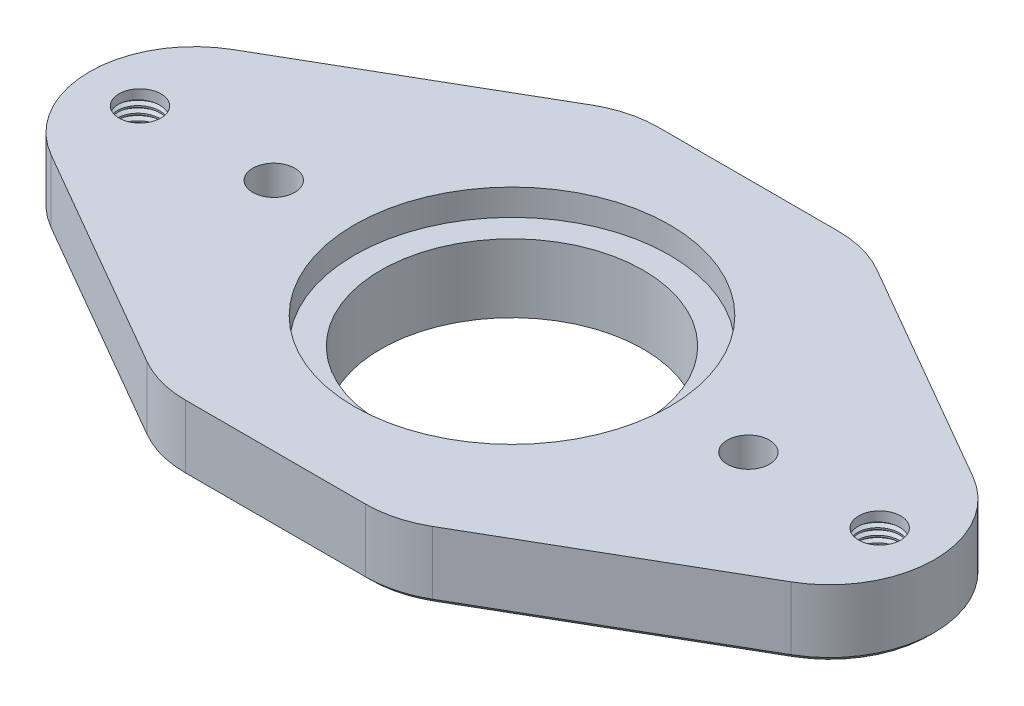
SolidWorks part; units mm, degrees
ref_plane "Plano frontal" through (0, 0, 0) normal (0, 0, 1) x (1, 0, 0)
ref_plane "Plano superior" through (0, 0, 0) normal (0, 1, 0) x (1, 0, 0)
ref_plane "Plano direito" through (0, 0, 0) normal (1, 0, 0) x (0, 0, -1)
sketch "Esboço1" plane through (0, 0, 0) normal (0, 1, 0) x (1, 0, 0)
  line L0 (22.5, 45) -> (100.4423, 0)
  line L1 (-22.5, 45) -> (22.5, 45)
  line L3 (-22.5, -45) -> (22.5, -45)
  line L5 (-22.5, 45) -> (22.5, -45) construction
  line L6 (-22.5, -45) -> (22.5, 45) construction
  line L7 (100.4423, 0) -> (22.5, -45)
  line L8 (-22.5, 45) -> (-100.4423, 0)
  line L9 (-22.5, -45) -> (-100.4423, 0)
  line L10 (0, 51.2716) -> (0, -62.3374) construction
  line L11 (-115.2689, 0) -> (116.7443, 0) construction
  point P0 (0, 0)
  dimension "D1" = 45
  dimension "D2" = 90
  dimension "D3" = 90
  dimension "D4" = 90
  dimension "D5" = 90
  dimension "D6" = 90
  dimension "D7" = 200.8846
extrude "Ressalto-extrusão1" add sketch "Esboço1" along normal blind 18
fillet "Filete1" radius 20 1 edges at (-100.4423, 9, 0)
fillet "Filete2" radius 20 1 edges at (-22.5, 9, 45)
fillet "Filete3" radius 20 1 edges at (22.5, 9, 45)
fillet "Filete4" radius 20 1 edges at (100.4423, 9, 0)
fillet "Filete5" radius 20 1 edges at (22.5, 9, -45)
fillet "Filete6" radius 20 1 edges at (-22.5, 9, -45)
sketch "Esboço2" plane through (0, 0, 0) normal (0, 1, 0) x (1, 0, 0)
  line L0 (-95.225, 0) -> (82.7172, 0) construction
  line L1 (-17.5, 35) -> (17.5, 35)
  line L3 (-17.5, -35) -> (17.5, -35)
  line L5 (-17.5, 35) -> (17.5, -35) construction
  line L6 (-17.5, -35) -> (17.5, 35) construction
  line L7 (17.5, -35) -> (78.1218, 0)
  line L8 (78.1218, 0) -> (17.5, 35)
  line L9 (-17.5, -35) -> (-78.1218, 0)
  line L10 (-78.1218, 0) -> (-17.5, 35)
  point P0 (0, 0)
  dimension "D1" = 70
  dimension "D2" = 35
  dimension "D3" = 70
  dimension "D4" = 70
  dimension "D5" = 70
  dimension "D6" = 70
extrude "Corte-extrusão1" cut sketch "Esboço2" along normal blind 5 flip side to cut
fillet "Filete7" radius 20 1 edges at (-17.5, 2.5, -35)
fillet "Filete8" radius 20 1 edges at (17.5, 2.5, -35)
fillet "Filete9" radius 20 1 edges at (78.1218, 2.5, 0)
fillet "Filete10" radius 20 1 edges at (-78.1218, 2.5, 0)
fillet "Filete11" radius 20 1 edges at (-17.5, 2.5, 35)
fillet "Filete12" radius 20 1 edges at (17.5, 2.5, 35)
sketch "Esboço3" plane through (0, 0, 0) normal (0, -1, 0) x (1, 0, 0)
  line L0 (0, 51.4475) -> (0, -49.7955) construction
  line L1 (-88.6171, 0.826) -> (83.6612, 0.826) construction
  line L2 (-70, 8.4959) -> (-70, -5.6639) construction
  line L3 (-45, 6.3719) -> (-45, -5.6639) construction
  circle A0 centre (-45, 0.354) radius 4
  circle A1 centre (-70, 0.826) radius 4
  dimension "D3" = 8
  dimension "D4" = 8
  dimension "D1" = 45
  dimension "D2" = 70
extrude "Corte-extrusão2" cut sketch "Esboço3" against normal blind 19 contours A1 | A0
sketch "Esboço4" plane through (0, 0, 0) normal (0, 1, 0) x (1, 0, 0)
  line L0 (-83.8971, 0) -> (85.3131, 0) construction
  line L1 (0, -48.6062) -> (0, 52.999) construction
  line L2 (45, -4.827) -> (45, 7.8151) construction
  line L3 (70, -4.827) -> (70, 7.8151) construction
  circle A0 centre (45, 0) radius 4
  circle A1 centre (70, 0) radius 4
  dimension "D3" = 8
  dimension "D4" = 8
  dimension "D1" = 45
  dimension "D2" = 70
extrude "Corte-extrusão4" cut sketch "Esboço4" along normal blind 19
sketch "Esboço5" plane through (0, 18, 0) normal (0, 1, 0) x (1, 0, 0)
  circle A0 centre (0, 0) radius 25
  dimension "D1" = 50
extrude "Corte-extrusão5" cut sketch "Esboço5" against normal blind 19
sketch "Esboço6" plane through (0, 18, 0) normal (0, 1, 0) x (1, 0, 0)
  circle A0 centre (0, 0) radius 30
  dimension "D1" = 60
extrude "Corte-extrusão6" cut sketch "Esboço6" against normal blind 5
sketch "Esboço8" plane through (0, 0, 0) normal (0, 0, 1) x (1, 0, 0)
  line L0 (-25, 0) -> (25, 0) construction
  line L1 (30, -0.5) -> (28, -0.5)
  line L2 (30, -0.5) -> (30, 1.5)
  line L3 (30, 1.5) -> (28, 1.5)
  line L4 (28, -0.5) -> (28, 1.5)
  line L5 (0, -5.8797) -> (0, 20.9238) construction
  dimension "D1" = 28
  dimension "D2" = 2
  dimension "D3" = 1.5
revolve "Corte-Revolução1" cut sketch "Esboço8" angle 360 about L5
chamfer "Chanfro1" distance 1 angle 45 28 edges at (45, 0, 4) (-45, 0, -3.646) (-70, 5, 4.826) (70, 5, 4) (0, 5, -45) (22.3174, 5, -44.3185) (-22.3174, 5, -44.3185) (48.7917, 5, -29.8205) (-48.7917, 5, -29.8205) (80.4423, 5, 0) (48.7917, 5, 29.8205) (22.3174, 5, 44.3185) (0, 5, 45) (-22.3174, 5, 44.3185) (-48.7917, 5, 29.8205) (-80.4423, 5, 0) (0, 0, -35) (-17.3174, 0, -34.3185) (17.3174, 0, -34.3185) (-35.1314, 0, -24.8205) (35.1314, 0, -24.8205) (-58.1218, 0, 0) (-35.1314, 0, 24.8205) (-17.3174, 0, 34.3185) (0, 0, 35) (17.3174, 0, 34.3185) (35.1314, 0, 24.8205) (58.1218, 0, 0)
thread "Rosca1" pitch 1.25 method cut profile "Perfil da rosca3" start angle 0, offset 0, length 10, pitch 1.25, diameter 8
ref_plane "Plano3" through (74, 6, 0) normal (0, 0, 1) x (1, 0, 0)
sketch "Perfil da rosca3" plane through (74, 6, 0) normal (0, 0, 1) x (1, 0, 0)
  line L0 (0, 0) -> (0, 1.25) construction
  line L1 (0, 0) -> (0.6766, 0.3906)
  line L2 (0.6766, 0.3906) -> (0.6766, 0.5469)
  line L3 (0.6766, 0.5469) -> (0, 0.9375)
  line L4 (0.6766, 0.4687) -> (0, 0.4687) construction
  line L11 (0, 0) -> (0, 0.9375)
  point P2 (0, 0)
  dimension "Pitch" = 1.25
  dimension "Profile_Angle" = 60
  dimension "Profile_Land" = 0.1562
  dimension "Profile_Height" = 0.6766
thread "Rosca2" pitch 1.25 method cut profile "Perfil da rosca4" start angle 0, offset 0, length 10, pitch 1.25, diameter 8
ref_plane "Plano4" through (-66, 6, 0.826) normal (0, 0, 1) x (1, 0, 0)
sketch "Perfil da rosca4" plane through (-66, 6, 0.826) normal (0, 0, 1) x (1, 0, 0)
  line L0 (0, 0) -> (0, 1.25) construction
  line L1 (0, 0) -> (0.6766, 0.3906)
  line L2 (0.6766, 0.3906) -> (0.6766, 0.5469)
  line L3 (0.6766, 0.5469) -> (0, 0.9375)
  line L4 (0.6766, 0.4687) -> (0, 0.4687) construction
  line L11 (0, 0) -> (0, 0.9375)
  point P2 (0, 0)
  dimension "Pitch" = 1.25
  dimension "Profile_Angle" = 60
  dimension "Profile_Land" = 0.1562
  dimension "Profile_Height" = 0.6766
